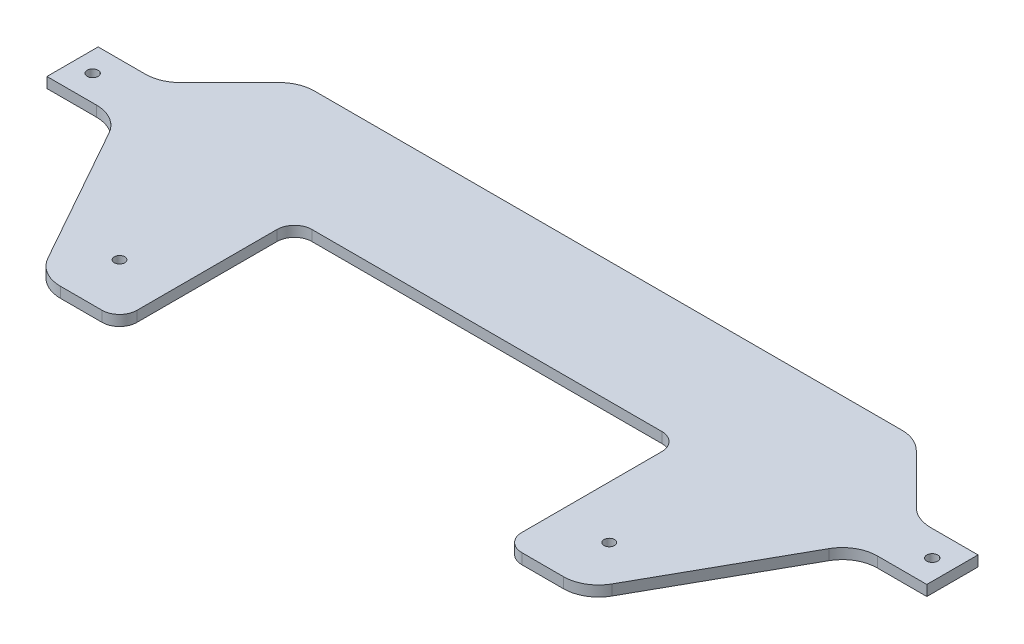
SolidWorks part; units mm, degrees
ref_plane "Alzado" through (0, 0, 0) normal (0, 0, 1) x (1, 0, 0)
ref_plane "Planta" through (0, 0, 0) normal (0, 1, 0) x (1, 0, 0)
ref_plane "Vista lateral" through (0, 0, 0) normal (1, 0, 0) x (0, 0, -1)
sketch "Croquis1" plane through (0, 0, 0) normal (0, 1, 0) x (1, 0, 0)
  line L0 (-27.8825, 0) -> (38.5584, 0) construction
  line L1 (-88.1, 42.3182) -> (88.1, 42.3182)
  line L2 (-77.75, -42.3182) -> (77.75, -42.3182)
  line L3 (-88.1, 42.3182) -> (-108.1, 22.3182)
  line L4 (-108.1, 22.3182) -> (-127.75, 22.3182)
  line L5 (0, 0) -> (0, 27.7067) construction
  line L6 (-127.75, 22.3182) -> (-127.75, 7.6818)
  line L7 (-127.75, 7.6818) -> (-105.75, 7.6818)
  line L8 (-105.75, 7.6818) -> (-77.75, -42.3182)
  line L9 (88.1, 42.3182) -> (108.1, 22.3182)
  line L10 (108.1, 22.3182) -> (127.75, 22.3182)
  line L11 (127.75, 22.3182) -> (127.75, 7.6818)
  line L12 (127.75, 7.6818) -> (105.75, 7.6818)
  line L13 (105.75, 7.6818) -> (77.75, -42.3182)
  dimension "D1" = 255.5
  dimension "D2" = 84.6363
  dimension "D3" = 19.65
  dimension "D4" = 22
  dimension "D5" = 22
  dimension "D6" = 50
  dimension "D7" = 50
  dimension "D8" = 50
  dimension "D9" = 20
  dimension "D10" = 20
extrude "Saliente-Extruir1" add sketch "Croquis1" along normal blind 3
fillet "Redondeo1" radius 10 8 edges at (88.1, 1.5, -42.3182) (-88.1, 1.5, -42.3182) (-77.75, 1.5, 42.3182) (77.75, 1.5, 42.3182) (108.1, 1.5, -22.3182) (105.75, 1.5, -7.6818) (-105.75, 1.5, -7.6818) (-108.1, 1.5, -22.3182)
sketch "Croquis2" plane through (0, 3, 0) normal (0, 1, 0) x (1, 0, 0)
  line L0 (0, 0) -> (0, -87.7887) construction
  line L1 (-119.9961, 22.3182) -> (-119.9961, 40.4374) construction
  line L2 (-112.2421, 22.3182) -> (-127.75, 22.3182) construction
  line L3 (-127.75, 15) -> (-123.2915, 15) construction
  line L4 (-127.75, 22.3182) -> (-127.75, 7.6818) construction
  line L5 (119.9961, 22.3182) -> (119.9961, 29.1715) construction
  line L6 (127.75, 22.3182) -> (112.2421, 22.3182) construction
  line L7 (115.6048, 15) -> (126.3231, 15) construction
  line L10 (-71.8888, -42.3182) -> (71.8888, -42.3182) construction
  circle A0 centre (70, -27.3182) radius 1.5
  circle A1 centre (-70, -27.3182) radius 1.5
  circle A2 centre (-119.9961, 15) radius 1.55
  circle A3 centre (119.9961, 15) radius 1.55
  circle A6 centre (-17.5, -17.3182) radius 1.5
  circle A7 centre (17.5, -17.3182) radius 1.5
  circle A8 centre (-17.5, -37.3182) radius 1.5
  circle A9 centre (17.5, -37.3182) radius 1.5
  dimension "D1" = 3.1
  dimension "D2" = 3.1
  dimension "D10" = 3
  dimension "D11" = 3
  dimension "D17" = 3
  dimension "D18" = 3
  dimension "D19" = 3
  dimension "D20" = 3
  dimension "D9" = 140
  dimension "D12" = 15
  dimension "D13" = 35
  dimension "D14" = 35
  dimension "D15" = 5
  dimension "D16" = 20
extrude "Cortar-Extruir1" cut sketch "Croquis2" against normal through all
sketch "Croquis4" plane through (0, 3, 0) normal (0, 1, 0) x (1, 0, 0)
  line L0 (-55, -42.3182) -> (-55, 7.6818)
  line L1 (-55, 7.6818) -> (55, 7.6818)
  line L2 (55, 7.6818) -> (55, -42.3182)
  line L3 (55, -42.3182) -> (-55, -42.3182)
  line L4 (0, 0) -> (0, 21.6247) construction
  line L5 (-71.8888, -42.3182) -> (71.8888, -42.3182) construction
  dimension "D1" = 110
  dimension "D2" = 50
extrude "Cortar-Extruir2" cut sketch "Croquis4" against normal through all
fillet "Redondeo2" radius 5 4 edges at (-55, 1.5, 42.3182) (55, 1.5, 42.3182) (55, 1.5, -7.6818) (-55, 1.5, -7.6818)
sketch "Croquis5" plane through (0, 3, 0) normal (0, 1, 0) x (1, 0, 0)
  line L0 (-127.75, 22.3182) -> (-127.75, 7.6818)
  line L1 (-127.75, 7.6818) -> (-123.75, 7.6818)
  line L2 (-127.75, 7.6818) -> (-111.6112, 7.6818) construction
  line L3 (-123.75, 7.6818) -> (-123.75, 22.3182)
  line L4 (-112.2421, 22.3182) -> (-127.75, 22.3182) construction
  line L5 (-123.75, 22.3182) -> (-127.75, 22.3182)
  line L6 (127.75, 22.3182) -> (127.75, 7.6818)
  line L7 (127.75, 7.6818) -> (123.75, 7.6818)
  line L8 (111.6112, 7.6818) -> (127.75, 7.6818) construction
  line L9 (123.75, 7.6818) -> (123.75, 22.3182)
  line L10 (127.75, 22.3182) -> (112.2421, 22.3182) construction
  line L11 (123.75, 22.3182) -> (127.75, 22.3182)
  dimension "D1" = 4
  dimension "D2" = 4
extrude "Cortar-Extruir3" cut sketch "Croquis5" against normal through all
sketch "Croquis6" plane through (123.75, 0, 0) normal (1, 0, 0) x (0, 0, -1)
  line L0 (7.6818, 3) -> (22.3182, 3)
  line L1 (22.3182, 3) -> (22.3182, 0)
  line L2 (22.3182, 0) -> (7.6818, 0)
  line L3 (22.3182, 0) -> (7.6818, 0) construction
  line L4 (7.6818, 0) -> (7.6818, 3) construction
  line L5 (7.6818, 3) -> (7.6818, 0)
extrude "Saliente-Extruir2" add sketch "Croquis6" along normal blind 2
sketch "Croquis8" plane through (-123.75, 0, 0) normal (-1, 0, 0) x (0, 0, 1)
  line L4 (-7.6818, 3) -> (-22.3182, 3)
  line L5 (-22.3182, 3) -> (-22.3182, 0)
  line L6 (-22.3182, 0) -> (-7.6818, 0)
  line L7 (-7.6818, 0) -> (-7.6818, 3)
  line L8 (-7.6818, 3) -> (-22.3182, 3)
  line L9 (-22.3182, 3) -> (-22.3182, 0)
  line L10 (-22.3182, 0) -> (-7.6818, 0)
  line L11 (-7.6818, 0) -> (-7.6818, 3)
  dimension "D1" = 0
extrude "Saliente-Extruir3" add sketch "Croquis8" along normal blind 2
